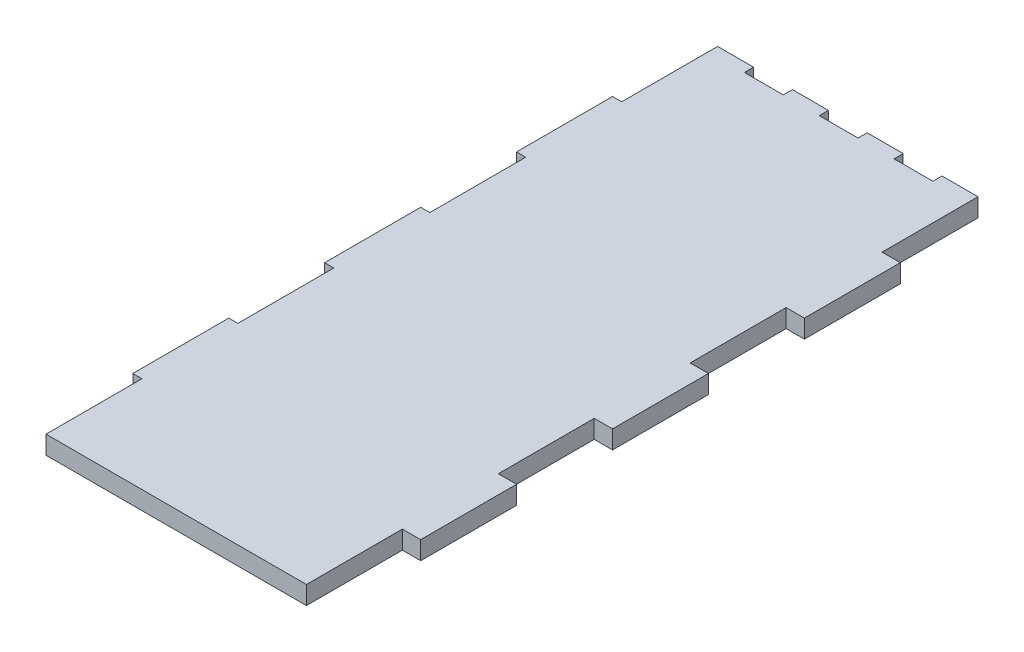
SolidWorks part; units mm, degrees
ref_plane "前视基准面" through (0, 0, 0) normal (0, 0, 1) x (1, 0, 0)
ref_plane "上视基准面" through (0, 0, 0) normal (0, 1, 0) x (1, 0, 0)
ref_plane "右视基准面" through (0, 0, 0) normal (1, 0, 0) x (0, 0, -1)
other "Configuration Table"
sketch "草图4" plane through (0, 0, 0) normal (0, 1, 0) x (1, 0, 0)
  line L6 (-28.5, -72.5) -> (28.5, -72.5)
  line L11 (-28.5, -72.5) -> (-28.5, 72.5)
  line L12 (-28.5, 72.5) -> (28.5, 72.5)
  line L13 (28.5, -72.5) -> (28.5, 72.5)
  line L14 (-28.5, -72.5) -> (28.5, 72.5) construction
  line L15 (-28.5, 72.5) -> (28.5, -72.5) construction
  point P0 (0, 0)
  dimension "D1" = 57
  dimension "D2" = 145
extrude "凸台-拉伸1" add sketch "草图4" along normal blind 4
sketch "草图5" plane through (0, 0, -72.5) normal (0, 0, -1) x (-1, 0, 0)
  line L0 (-28.5, 4) -> (28.5, 4) construction
  line L1 (28.5, 0) -> (20.625, 0)
  line L2 (28.5, 0) -> (28.5, 4)
  line L3 (28.5, 4) -> (20.625, 4)
  line L4 (20.625, 0) -> (20.625, 4)
  line L5 (-28.5, 0) -> (28.5, 0) construction
  line L6 (12.125, 0) -> (4.25, 0)
  line L7 (12.125, 0) -> (12.125, 4)
  line L8 (12.125, 4) -> (4.25, 4)
  line L9 (4.25, 0) -> (4.25, 4)
  line L10 (20.625, 0) -> (12.125, 0)
  line L11 (-4.25, 0) -> (-12.125, 0)
  line L12 (-4.25, 0) -> (-4.25, 4)
  line L13 (-4.25, 4) -> (-12.125, 4)
  line L14 (-12.125, 0) -> (-12.125, 4)
  line L15 (-20.625, 0) -> (-28.5, 0)
  line L16 (-20.625, 0) -> (-20.625, 4)
  line L17 (-20.625, 4) -> (-28.5, 4)
  line L18 (-28.5, 0) -> (-28.5, 4)
  line L19 (4.25, 0) -> (-4.25, 0)
  line L20 (-12.125, 0) -> (-20.625, 0)
  line M17 (-28.5, 0) -> (28.5, 0)
  line M18 (28.5, 0) -> (28.5, 4)
  line M19 (28.5, 4) -> (-28.5, 4)
  line M20 (-28.5, 4) -> (-28.5, 0)
  dimension "D1" = 8.5
extrude "凸台-拉伸2" add sketch "草图5" along normal blind 2 contours L16 M17 M19 M20 | L14 L12 M17 M19 | L9 L7 M17 M19 | L4 M17 M18 M19 region at (-24.5625, 2, -72.5) region at (-8.1875, 2, -72.5) region at (8.1875, 2, -72.5) region at (24.5625, 2, -72.5)
sketch "草图6" plane through (-28.5, 0, 0) normal (-1, 0, 0) x (0, 0, 1)
  line L0 (-74.5, 4) -> (72.5, 4) construction
  line L1 (-53.5, 4) -> (-32.5, 4)
  line L2 (-53.5, 4) -> (-53.5, 0)
  line L3 (-53.5, 0) -> (-32.5, 0)
  line L4 (-32.5, 4) -> (-32.5, 0)
  line L5 (-74.5, 0) -> (72.5, 0) construction
  line L6 (-74.5, 2) -> (-53.5, 2) construction
  line L7 (-11.5, 4) -> (9.5, 4)
  line L8 (-11.5, 4) -> (-11.5, 0)
  line L9 (-11.5, 0) -> (9.5, 0)
  line L10 (9.5, 4) -> (9.5, 0)
  line L11 (30.5, 4) -> (51.5, 4)
  line L12 (30.5, 4) -> (30.5, 0)
  line L13 (30.5, 0) -> (51.5, 0)
  line L14 (51.5, 4) -> (51.5, 0)
  line L15 (-74.5, 0) -> (-74.5, 4) construction
  line L16 (-53.5, 2) -> (-32.5, 2) construction
  line L17 (-32.5, 2) -> (-11.5, 2) construction
  line L18 (-11.5, 2) -> (9.5, 2) construction
  line L19 (9.5, 2) -> (30.5, 2) construction
  line L20 (30.5, 2) -> (51.5, 2) construction
  line L21 (51.5, 2) -> (72.5, 2) construction
  line L22 (72.5, 4) -> (72.5, 0) construction
extrude "凸台-拉伸3" add sketch "草图6" along normal blind 2
extrude "凸台-拉伸4" add sketch "草图6<2>" against normal blind 4 from surface starting at face at (28.5, 2, -1)
sketch "草图6<2>" plane through (-28.5, 0, 0) normal (-1, 0, 0) x (0, 0, 1) same geometry as "草图6"
sketch "草图7" plane through (0, 0, 72.5) normal (0, 0, 1) x (1, 0, 0)
  line L0 (-10.3, 0) -> (-12.5, 2.2)
  line L1 (-28.5, 0) -> (28.5, 0) construction
  line L2 (-12.5, 2.2) -> (-10.3, 2.2)
  line L3 (-10.3, 2.2) -> (10.3, 2.2)
  line L4 (10.3, 2.2) -> (12.5, 2.2)
  line L5 (12.5, 2.2) -> (10.3, 0)
  line L6 (10.3, 0) -> (-10.3, 0)
  line L7 (-10.3, 2.2) -> (-10.3, 0)
  line L8 (10.3, 2.2) -> (10.3, 0)
  line L9 (0, 0) -> (0, 2.2) construction
  line L10 (-30.5, 0) -> (-30.5, 4) construction
  line L11 (32.5, 0) -> (32.5, 4) construction
  line M10 (-28.5, 0) -> (28.5, 0)
  dimension "D1" = 20.6
  dimension "D2" = 2.2
  dimension "D3" = 30.5
  dimension "D4" = 32.5
extrude "切除-拉伸1" cut sketch "草图7" against normal through all from offset 1.8 contours L7 L2 L0 | L9 L3 L7 M10 | L9 L6 L8 L3 | L4 L8 L5 region at (-5.15, 1.1, 72.5) region at (-11.0333, 1.4667, 72.5) region at (5.15, 1.1, 72.5) region at (11.0333, 1.4667, 72.5) offset against normal yes
sketch "草图8" plane through (0, 2.2, 0) normal (0, -1, 0) x (1, 0, 0)
  line L0 (-16.375, -72.5) -> (-10.3, -54.5)
  line L1 (-12.125, -72.5) -> (-20.625, -72.5) construction
  line L2 (-10.3, -74.5) -> (-10.3, 70.7) construction
  line L3 (-10.3, -54.5) -> (10.3, -54.5)
  line L4 (10.3, -74.5) -> (10.3, 70.7) construction
  line L5 (10.3, -54.5) -> (16.375, -72.5)
  line L6 (20.625, -72.5) -> (12.125, -72.5) construction
  line L7 (-20.625, -74.5) -> (-28.5, -74.5) construction
  line L8 (-16.375, -72.5) -> (16.375, -72.5)
  line L9 (-16.375, -72.5) -> (-16.375, -74.5)
  line L10 (-16.375, -74.5) -> (16.375, -74.5)
  line L11 (16.375, -72.5) -> (16.375, -74.5)
  line M7 (-12.5, 70.7) -> (-12.5, -72.5)
  line M8 (-12.5, -72.5) -> (-12.125, -72.5)
  line M12 (-4.25, -72.5) -> (4.25, -72.5)
  line M16 (12.125, -72.5) -> (12.5, -72.5)
  line M17 (12.5, -72.5) -> (12.5, 70.7)
  dimension "D1" = 20
extrude "切除-拉伸2" cut sketch "草图8" along normal through all contours L0 L8 M7 | L8 L5 L3 L0 M8 M12 M16 M17 M7 | L8 L5 M17 | L9 L10 L11 L8 region at (-13.7917, 2.2, -68.6728) region at (0, 2.2, -63.7247) region at (13.7917, 2.2, -68.6728)
